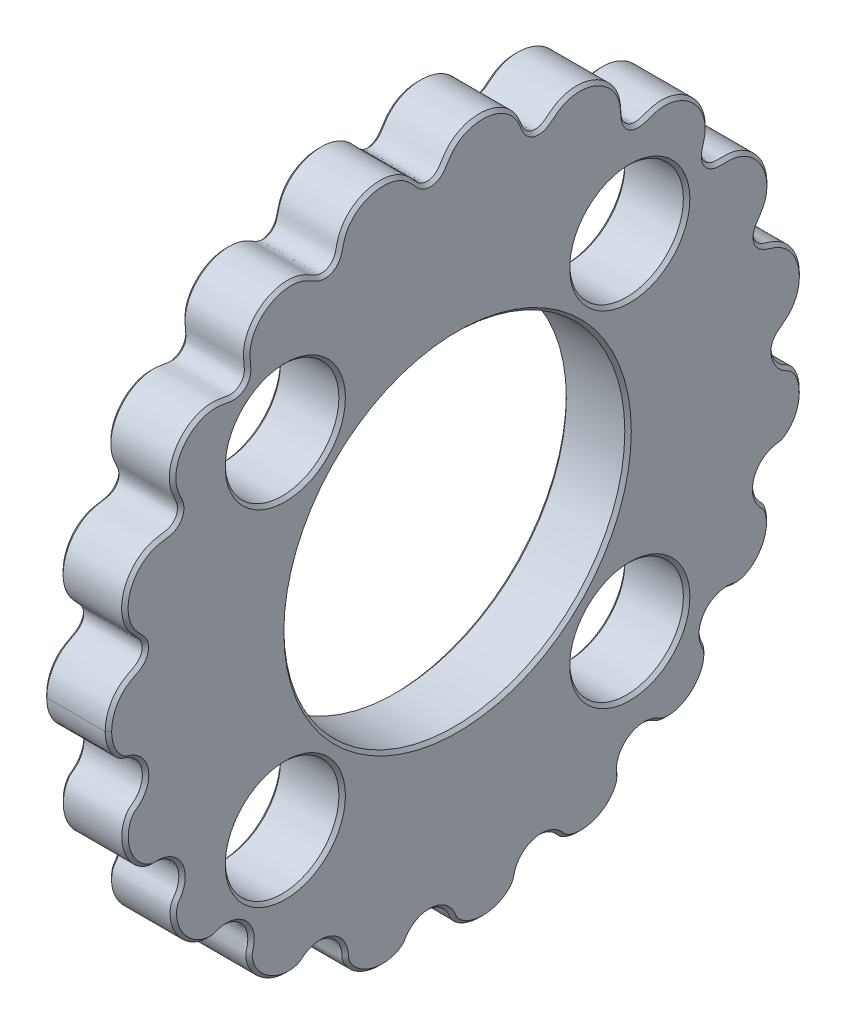
SolidWorks part; units mm, degrees
ref_plane "Ebene vorne" through (0, 0, 0) normal (0, 0, 1) x (1, 0, 0)
ref_plane "Ebene oben" through (0, 0, 0) normal (0, 1, 0) x (1, 0, 0)
ref_plane "Ebene rechts" through (0, 0, 0) normal (1, 0, 0) x (0, 0, -1)
sketch "Sketch3" plane through (0, 0, 0) normal (1, 0, 0) x (0, 0, -1)
  line L0 (-69.959, 0) -> (69.959, 0) construction
  line L1 (0, 0) -> (-10.6066, 10.6066) construction
  circle A0 centre (0, 0) radius 15
  circle A1 centre (-10.6066, 10.6066) radius 3.5
  circle A2 centre (10.6066, 10.6066) radius 3.5
  circle A3 centre (10.6066, -10.6066) radius 3.5
  circle A4 centre (-10.6066, -10.6066) radius 3.5
  circle A5 centre (0, 0) radius 10.5
  spline S0 degree 4 poles (20.1598, 5.1766) (20.2489, 5.1264) (20.4175, 5.0093) (20.6743, 4.7658) (20.9574, 4.3512) (21.1652, 3.8448) (21.2528, 3.3342) (21.2472, 2.8914) (21.1835, 2.5096) (21.0997, 2.2356) (20.9932, 1.9994) (20.8724, 1.8019) (20.7735, 1.6733) (20.6777, 1.5726) (20.5896, 1.4977) (20.5132, 1.4449) (20.4297, 1.4047) (20.3465, 1.3647) (20.2541, 1.3135) (20.1541, 1.2498) (20.0201, 1.1487) (19.8899, 1.0222) (19.7767, 0.8808) (19.6825, 0.7257) (19.6193, 0.5964) (19.5727, 0.4698) (19.5402, 0.3554) (19.5187, 0.2421) (19.5059, 0.1552) (19.4993, 0.0318) (19.4995, -0.0375) (19.5068, -0.1675) (19.5215, -0.258) (19.5435, -0.3688) (19.5726, -0.4665) (19.6088, -0.5678) (19.6518, -0.6633) (19.7141, -0.7811) (19.8021, -0.9144) (19.9055, -1.0376) (20.0225, -1.1477) (20.1279, -1.2303) (20.2164, -1.2904) (20.3096, -1.3452) (20.4065, -1.3948) (20.5072, -1.4399) (20.5986, -1.5037) (20.7026, -1.5958) (20.8136, -1.7205) (20.9519, -1.9189) (21.0919, -2.2037) (21.1991, -2.5525) (21.253, -2.9608) (21.242, -3.3883) (21.1596, -3.8246) (20.9993, -4.2562) (20.7847, -4.6139) (20.5518, -4.8847) (20.3196, -5.082) (20.148, -5.1902) (20.0018, -5.2562) (19.889, -5.2886) (19.823, -5.3) (19.7398, -5.3091) (19.6403, -5.323) (19.4926, -5.3532) (19.2396, -5.4344) (18.9193, -5.6134) (18.6087, -5.9329) (18.3998, -6.371) (18.3434, -6.7729) (18.3754, -7.0976) (18.4524, -7.3578) (18.5433, -7.556) (18.6476, -7.7183) (18.7538, -7.8482) (18.8534, -7.9501) (18.9388, -8.0314) (19.0057, -8.129) (19.0617, -8.2323) (19.1194, -8.3679) (19.1853, -8.5813) (19.2316, -8.8783) (19.2272, -9.2552) (19.1492, -9.6716) (19.0013, -10.0803) (18.7836, -10.4696) (18.4965, -10.8258) (18.141, -11.132) (17.8062, -11.3203) (17.5245, -11.4181) (17.3161, -11.4556) (17.1899, -11.4659) (17.0628, -11.4599) (16.9399, -11.4279) (16.784, -11.4013) (16.5943, -11.3863) (16.3722, -11.3993) (16.062, -11.4694) (15.7287, -11.6282) (15.4102, -11.9026) (15.166, -12.3004) (15.0661, -12.6812) (15.0617, -13.0152) (15.1059, -13.2618) (15.1556, -13.4248) (15.2052, -13.5453) (15.2437, -13.6271) (15.2853, -13.7075) (15.3299, -13.8198) (15.3611, -13.9838) (15.3718, -14.2441) (15.3234, -14.5815) (15.2018, -14.9515) (14.9918, -15.3365) (14.7188, -15.6829) (14.3906, -15.9822) (14.0151, -16.2248) (13.6521, -16.3784) (13.3247, -16.4596) (13.0704, -16.4859) (12.896, -16.486) (12.747, -16.4725) (12.6248, -16.4497) (12.5044, -16.4166) (12.3914, -16.3634) (12.2876, -16.2945) (12.1769, -16.2375) (12.0639, -16.1864) (11.9469, -16.1455) (11.798, -16.1056) (11.6151, -16.0774) (11.3989, -16.0731) (11.1004, -16.1161) (10.7645, -16.2398) (10.4271, -16.4766) (10.1791, -16.7994) (10.0441, -17.1159) (9.9845, -17.3978) (9.9735, -17.6032) (9.9836, -17.7825) (10.0093, -17.9343) (10.0096, -18.0577) (9.9909, -18.1796) (9.962, -18.2991) (9.9142, -18.4395) (9.8438, -18.5981) (9.7171, -18.8194) (9.5108, -19.0856) (9.2242, -19.3554) (8.8509, -19.6009) (8.4446, -19.7806) (8.0172, -19.8906) (7.5794, -19.9274) (7.192, -19.8889) (6.8645, -19.7971) (6.6325, -19.6823) (6.4834, -19.5805) (6.3828, -19.4695) (6.3085, -19.3763) (6.2049, -19.2713) (6.0725, -19.1566) (5.9023, -19.0444) (5.6924, -18.9467) (5.4174, -18.8669) (5.0761, -18.8384) (4.6713, -18.9063) (4.3021, -19.0948) (4.0341, -19.3363) (3.853, -19.5884) (3.7553, -19.7851) (3.6942, -19.965) (3.6579, -20.1211) (3.6359, -20.2479) (3.5855, -20.3669) (3.5231, -20.4788) (3.4349, -20.6053) (3.3176, -20.7414) (3.1252, -20.9211) (2.8393, -21.1182) (2.4722, -21.2912) (2.0318, -21.409) (1.5853, -21.4507) (1.1457, -21.4191) (0.7242, -21.3171) (0.3736, -21.162) (0.0963, -20.9776) (-0.0868, -20.8033) (-0.1954, -20.6677) (-0.2653, -20.5409) (-0.3023, -20.4313) (-0.3582, -20.3022) (-0.4357, -20.1551) (-0.5755, -19.9522) (-0.8096, -19.7201) (-1.1429, -19.5201) (-1.5298, -19.4209) (-1.8833, -19.4216) (-2.1824, -19.4863) (-2.4235, -19.5837) (-2.6177, -19.704) (-2.7683, -19.83) (-2.8819, -19.949) (-2.9651, -20.0526) (-3.0308, -20.1486) (-3.0815, -20.2343) (-3.1318, -20.3203) (-3.2149, -20.4245) (-3.3463, -20.5413) (-3.5281, -20.6607) (-3.8009, -20.7896) (-4.1396, -20.8903) (-4.5495, -20.9403) (-5.0055, -20.9124) (-5.4359, -20.8119) (-5.831, -20.6497) (-6.1835, -20.435) (-6.4602, -20.1949) (-6.6471, -19.9716) (-6.762, -19.789) (-6.8259, -19.6634) (-6.8684, -19.559) (-6.902, -19.4512) (-6.9203, -19.3396) (-6.9202, -19.2272) (-6.9287, -19.116) (-6.9432, -19.0058) (-6.9653, -18.8974) (-7.0023, -18.7642) (-7.0618, -18.609) (-7.176, -18.393) (-7.3782, -18.1405) (-7.6456, -17.9326) (-7.9665, -17.7915) (-8.2726, -17.7292) (-8.5479, -17.7238) (-8.7862, -17.7624) (-8.9831, -17.8259) (-9.1403, -17.8978) (-9.2605, -17.9671) (-9.3756, -18.0454) (-9.4814, -18.1347) (-9.5867, -18.2261) (-9.7115, -18.2894) (-9.8659, -18.3496) (-10.0545, -18.3955) (-10.2734, -18.4226) (-10.5217, -18.4222) (-10.8297, -18.3877) (-11.191, -18.2958) (-11.5863, -18.1244) (-11.9914, -17.8524) (-12.3379, -17.5156) (-12.5789, -17.1733) (-12.7328, -16.8493) (-12.8091, -16.5879) (-12.841, -16.4031) (-12.8477, -16.2421) (-12.8408, -16.1054) (-12.8012, -15.975) (-12.762, -15.8451) (-12.7361, -15.7115) (-12.72, -15.5767) (-12.7133, -15.3409) (-12.762, -15.0062) (-12.9287, -14.6233) (-13.2603, -14.2612) (-13.6131, -14.0585) (-13.9228, -13.9677) (-14.1874, -13.9415) (-14.3979, -13.9495) (-14.5819, -13.9821) (-14.7389, -14.0276) (-14.8688, -14.0787) (-14.9772, -14.1217) (-15.0926, -14.141) (-15.2084, -14.1497) (-15.354, -14.1467) (-15.5742, -14.1203) (-15.8631, -14.0426) (-16.2049, -13.8866) (-16.5536, -13.6476) (-16.8676, -13.3477) (-17.1359, -12.9915) (-17.3463, -12.5846) (-17.4827, -12.1351) (-17.5233, -11.7179) (-17.4872, -11.3856) (-17.4137, -11.1474) (-17.3356, -11.0026) (-17.2532, -10.9001) (-17.1662, -10.7612) (-17.0775, -10.5876) (-17.0048, -10.3733) (-16.953, -10.0569) (-16.9754, -9.6908) (-17.108, -9.2976) (-17.3815, -8.9223) (-17.6948, -8.6844) (-18.0059, -8.5517) (-18.2577, -8.4983) (-18.4304, -8.484) (-18.5768, -8.4833) (-18.6963, -8.4942) (-18.846, -8.4822) (-19.02, -8.4351) (-19.2565, -8.3348) (-19.5373, -8.1524) (-19.8177, -7.8936) (-20.0766, -7.552) (-20.2797, -7.1665) (-20.4201, -6.7458) (-20.4899, -6.3001) (-20.4812, -5.8985) (-20.4188, -5.5606) (-20.3355, -5.3148) (-20.2618, -5.1556) (-20.1868, -5.0267) (-20.1153, -4.9277) (-20.0353, -4.834) (-19.9381, -4.7591) (-19.8365, -4.6909) (-19.7422, -4.6127) (-19.6292, -4.5071) (-19.507, -4.3649) (-19.3869, -4.1805) (-19.286, -3.9488) (-19.2151, -3.6655) (-19.2002, -3.3332) (-19.2616, -3.0164) (-19.3873, -2.7331) (-19.5327, -2.5197) (-19.672, -2.3657) (-19.8304, -2.2321) (-19.9833, -2.1352) (-20.1221, -2.0671) (-20.2418, -2.0207) (-20.3392, -1.9882) (-20.4387, -1.9626) (-20.5341, -1.9237) (-20.6351, -1.8649) (-20.7411, -1.7884) (-20.8788, -1.6657) (-21.0357, -1.486) (-21.1893, -1.254) (-21.314, -0.9913) (-21.3989, -0.7437) (-21.4473, -0.5393) (-21.4733, -0.3884) (-21.4883, -0.2556) (-21.4963, -0.1623) (-21.5004, -0.0324) (-21.5003, 0.0419) (-21.4955, 0.1832) (-21.4855, 0.2823) (-21.4707, 0.4047) (-21.4508, 0.5144) (-21.4198, 0.657) (-21.3725, 0.8223) (-21.3028, 1.0125) (-21.2028, 1.2203) (-21.0822, 1.4173) (-20.9568, 1.5792) (-20.8332, 1.7075) (-20.7176, 1.8065) (-20.6146, 1.8778) (-20.5048, 1.9405) (-20.3843, 1.9771) (-20.2637, 2.0114) (-20.1466, 2.0573) (-20.0068, 2.1227) (-19.8498, 2.2182) (-19.6838, 2.3514) (-19.5215, 2.5308) (-19.363, 2.7742) (-19.2381, 3.0912) (-19.1788, 3.5444) (-19.2823, 4.0223) (-19.4989, 4.3828) (-19.7335, 4.6102) (-19.8718, 4.7151) (-19.943, 4.7645) (-19.9775, 4.7908) (-19.9945, 4.8043) knots 0 0 0 0 0 0.00445 0.008901 0.015291 0.021681 0.028072 0.031267 0.034462 0.038485 0.040497 0.042509 0.04452 0.045526 0.046532 0.047538 0.048544 0.049549 0.050555 0.052128 0.053701 0.056847 0.058419 0.059992 0.061565 0.063138 0.06421 0.065282 0.066355 0.067427 0.068575 0.069724 0.070872 0.072021 0.073169 0.074318 0.075467 0.076615 0.078942 0.08127 0.082433 0.083597 0.08476 0.085924 0.087131 0.088338 0.089545 0.090753 0.093167 0.095581 0.100042 0.104502 0.108963 0.113423 0.118578 0.123733 0.128888 0.131466 0.134043 0.136956 0.137684 0.138412 0.13914 0.139868 0.141325 0.142781 0.145694 0.1514 0.157107 0.161784 0.166461 0.168825 0.171189 0.173553 0.175916 0.177195 0.178475 0.179754 0.181033 0.182312 0.183591 0.186149 0.190735 0.195322 0.199908 0.204495 0.209568 0.214641 0.219714 0.224787 0.226163 0.227539 0.228915 0.230291 0.231667 0.233043 0.235794 0.23855 0.241306 0.246818 0.251681 0.256544 0.26132 0.263709 0.266097 0.267408 0.26872 0.269375 0.270031 0.271342 0.273965 0.276587 0.281332 0.286077 0.290822 0.295567 0.30044 0.305313 0.310187 0.312623 0.31506 0.316413 0.317766 0.319118 0.320471 0.321824 0.323176 0.324529 0.325882 0.32722 0.328558 0.331235 0.333911 0.336587 0.341625 0.346663 0.35157 0.354024 0.356477 0.359151 0.360488 0.361825 0.363162 0.364499 0.365835 0.367172 0.369606 0.372039 0.376905 0.381772 0.386639 0.391391 0.396144 0.400896 0.405649 0.408244 0.41084 0.412138 0.413436 0.414733 0.416031 0.418542 0.421052 0.423562 0.426073 0.430951 0.435829 0.441158 0.443823 0.446488 0.449278 0.450673 0.452068 0.453463 0.454858 0.456253 0.457648 0.460155 0.462663 0.467679 0.472695 0.47771 0.482404 0.487098 0.491792 0.496485 0.498994 0.501503 0.502758 0.504012 0.505266 0.506521 0.508878 0.511236 0.51595 0.520754 0.525557 0.528373 0.531188 0.534004 0.53682 0.538264 0.539709 0.541153 0.542597 0.543319 0.544041 0.545485 0.548374 0.550925 0.553476 0.558578 0.56368 0.568782 0.573252 0.577722 0.582192 0.586662 0.589112 0.590337 0.591563 0.592788 0.594013 0.595238 0.596463 0.597665 0.598868 0.60007 0.601273 0.603677 0.606082 0.610663 0.615244 0.618223 0.621202 0.624181 0.62716 0.628669 0.630178 0.631688 0.633197 0.634706 0.636215 0.637725 0.639234 0.641927 0.644619 0.647312 0.650005 0.65539 0.660775 0.665949 0.671124 0.676298 0.678885 0.681473 0.682949 0.684426 0.685902 0.687379 0.688856 0.690332 0.691809 0.693286 0.699103 0.704921 0.709604 0.714288 0.716571 0.718854 0.721138 0.723421 0.724685 0.72595 0.727214 0.728479 0.729743 0.731008 0.733537 0.738115 0.742692 0.74727 0.751847 0.756929 0.762011 0.767092 0.772174 0.775025 0.77645 0.777875 0.7793 0.780725 0.783576 0.786336 0.789097 0.794618 0.799358 0.804098 0.809026 0.81149 0.813954 0.815255 0.816556 0.817857 0.819158 0.82176 0.824362 0.829001 0.83364 0.83828 0.842919 0.847883 0.852848 0.857813 0.860295 0.862778 0.864108 0.865439 0.86677 0.868101 0.869431 0.870762 0.872093 0.873423 0.876159 0.878894 0.88163 0.884365 0.888808 0.893251 0.895503 0.897755 0.900008 0.90226 0.904493 0.905609 0.906725 0.907841 0.908958 0.910074 0.91119 0.912915 0.914639 0.918087 0.921535 0.924984 0.927236 0.929487 0.930613 0.931739 0.932865 0.933991 0.935244 0.936498 0.937752 0.939005 0.940259 0.941513 0.94402 0.946528 0.949035 0.951542 0.95405 0.955415 0.95678 0.958145 0.95951 0.960875 0.96224 0.963605 0.96497 0.96759 0.97021 0.97283 0.975451 0.980179 0.984906 0.992453 0.996227 0.998113 0.999057 1 1 1 1 1 construction
  spline S1 degree 4 poles (19.5, 0) (19.5, -0.0229) (19.5012, -0.0684) (19.5068, -0.1675) (19.5215, -0.258) (19.5435, -0.3688) (19.5726, -0.4665) (19.6088, -0.5678) (19.6518, -0.6633) (19.7141, -0.7811) (19.8021, -0.9144) (19.9055, -1.0376) (20.0225, -1.1477) (20.1279, -1.2303) (20.2164, -1.2904) (20.3096, -1.3452) (20.4065, -1.3948) (20.5072, -1.4399) (20.5986, -1.5037) (20.7026, -1.5958) (20.8136, -1.7205) (20.9519, -1.9189) (21.0919, -2.2037) (21.1991, -2.5525) (21.253, -2.9608) (21.242, -3.3883) (21.1596, -3.8246) (20.9993, -4.2562) (20.7847, -4.6139) (20.5518, -4.8847) (20.3196, -5.082) (20.148, -5.1902) (20.0018, -5.2562) (19.889, -5.2886) (19.823, -5.3) (19.7398, -5.3091) (19.6403, -5.323) (19.4926, -5.3532) (19.2396, -5.4344) (18.9193, -5.6134) (18.6087, -5.9329) (18.3998, -6.371) (18.3434, -6.7729) (18.3754, -7.0976) (18.4524, -7.3578) (18.5433, -7.556) (18.6476, -7.7183) (18.7538, -7.8482) (18.8534, -7.9501) (18.9388, -8.0314) (19.0057, -8.129) (19.0617, -8.2323) (19.1194, -8.3679) (19.1853, -8.5813) (19.2316, -8.8783) (19.2272, -9.2552) (19.1492, -9.6716) (19.0013, -10.0803) (18.7836, -10.4696) (18.4965, -10.8258) (18.141, -11.132) (17.8062, -11.3203) (17.5245, -11.4181) (17.3161, -11.4556) (17.1899, -11.4659) (17.0628, -11.4599) (16.9399, -11.4279) (16.784, -11.4013) (16.5943, -11.3863) (16.3722, -11.3993) (16.062, -11.4694) (15.7287, -11.6282) (15.4102, -11.9026) (15.166, -12.3004) (15.0661, -12.6812) (15.0617, -13.0152) (15.1059, -13.2618) (15.1556, -13.4248) (15.2052, -13.5453) (15.2437, -13.6271) (15.2853, -13.7075) (15.3299, -13.8198) (15.3611, -13.9838) (15.3718, -14.2441) (15.3234, -14.5815) (15.2018, -14.9515) (14.9918, -15.3365) (14.7188, -15.6829) (14.3906, -15.9822) (14.0151, -16.2248) (13.6521, -16.3784) (13.3247, -16.4596) (13.0704, -16.4859) (12.896, -16.486) (12.747, -16.4725) (12.6248, -16.4497) (12.5044, -16.4166) (12.3914, -16.3634) (12.2876, -16.2945) (12.1769, -16.2375) (12.0639, -16.1864) (11.9469, -16.1455) (11.798, -16.1056) (11.6151, -16.0774) (11.3989, -16.0731) (11.1004, -16.1161) (10.7645, -16.2398) (10.4271, -16.4766) (10.1791, -16.7994) (10.0441, -17.1159) (9.9845, -17.3978) (9.9735, -17.6032) (9.9836, -17.7825) (10.0093, -17.9343) (10.0096, -18.0577) (9.9909, -18.1796) (9.962, -18.2991) (9.9142, -18.4395) (9.8438, -18.5981) (9.7171, -18.8194) (9.5108, -19.0856) (9.2242, -19.3554) (8.8509, -19.6009) (8.4446, -19.7806) (8.0172, -19.8906) (7.5794, -19.9274) (7.192, -19.8889) (6.8645, -19.7971) (6.6325, -19.6823) (6.4834, -19.5805) (6.3828, -19.4695) (6.3085, -19.3763) (6.2049, -19.2713) (6.0725, -19.1566) (5.9023, -19.0444) (5.6924, -18.9467) (5.4174, -18.8669) (5.0761, -18.8384) (4.6713, -18.9063) (4.3021, -19.0948) (4.0341, -19.3363) (3.853, -19.5884) (3.7553, -19.7851) (3.6942, -19.965) (3.6579, -20.1211) (3.6359, -20.2479) (3.5855, -20.3669) (3.5231, -20.4788) (3.4349, -20.6053) (3.3176, -20.7414) (3.1252, -20.9211) (2.8393, -21.1182) (2.4722, -21.2912) (2.0318, -21.409) (1.5853, -21.4507) (1.1457, -21.4191) (0.7242, -21.3171) (0.3736, -21.162) (0.0963, -20.9776) (-0.0868, -20.8033) (-0.1954, -20.6677) (-0.2653, -20.5409) (-0.3023, -20.4313) (-0.3582, -20.3022) (-0.4357, -20.1551) (-0.5755, -19.9522) (-0.8096, -19.7201) (-1.1429, -19.5201) (-1.5298, -19.4209) (-1.8833, -19.4216) (-2.1824, -19.4863) (-2.4235, -19.5837) (-2.6177, -19.704) (-2.7683, -19.83) (-2.8819, -19.949) (-2.9651, -20.0526) (-3.0308, -20.1486) (-3.0815, -20.2343) (-3.1318, -20.3203) (-3.2149, -20.4245) (-3.3463, -20.5413) (-3.5281, -20.6607) (-3.8009, -20.7896) (-4.1396, -20.8903) (-4.5495, -20.9403) (-5.0055, -20.9124) (-5.4359, -20.8119) (-5.831, -20.6497) (-6.1835, -20.435) (-6.4602, -20.1949) (-6.6471, -19.9716) (-6.762, -19.789) (-6.8259, -19.6634) (-6.8684, -19.559) (-6.902, -19.4512) (-6.9203, -19.3396) (-6.9202, -19.2272) (-6.9287, -19.116) (-6.9432, -19.0058) (-6.9653, -18.8974) (-7.0023, -18.7642) (-7.0618, -18.609) (-7.176, -18.393) (-7.3782, -18.1405) (-7.6456, -17.9326) (-7.9665, -17.7915) (-8.2726, -17.7292) (-8.5479, -17.7238) (-8.7862, -17.7624) (-8.9831, -17.8259) (-9.1403, -17.8978) (-9.2605, -17.9671) (-9.3756, -18.0454) (-9.4814, -18.1347) (-9.5867, -18.2261) (-9.7115, -18.2894) (-9.8659, -18.3496) (-10.0545, -18.3955) (-10.2734, -18.4226) (-10.5217, -18.4222) (-10.8297, -18.3877) (-11.191, -18.2958) (-11.5863, -18.1244) (-11.9914, -17.8524) (-12.3379, -17.5156) (-12.5789, -17.1733) (-12.7328, -16.8493) (-12.8091, -16.5879) (-12.841, -16.4031) (-12.8477, -16.2421) (-12.8408, -16.1054) (-12.8012, -15.975) (-12.762, -15.8451) (-12.7361, -15.7115) (-12.72, -15.5767) (-12.7133, -15.3409) (-12.762, -15.0062) (-12.9287, -14.6233) (-13.2603, -14.2612) (-13.6131, -14.0585) (-13.9228, -13.9677) (-14.1874, -13.9415) (-14.3979, -13.9495) (-14.5819, -13.9821) (-14.7389, -14.0276) (-14.8688, -14.0787) (-14.9772, -14.1217) (-15.0926, -14.141) (-15.2084, -14.1497) (-15.354, -14.1467) (-15.5742, -14.1203) (-15.8631, -14.0426) (-16.2049, -13.8866) (-16.5536, -13.6476) (-16.8676, -13.3477) (-17.1359, -12.9915) (-17.3463, -12.5846) (-17.4827, -12.1351) (-17.5233, -11.7179) (-17.4872, -11.3856) (-17.4137, -11.1474) (-17.3356, -11.0026) (-17.2532, -10.9001) (-17.1662, -10.7612) (-17.0775, -10.5876) (-17.0048, -10.3733) (-16.953, -10.0569) (-16.9754, -9.6908) (-17.108, -9.2976) (-17.3815, -8.9223) (-17.6948, -8.6844) (-18.0059, -8.5517) (-18.2577, -8.4983) (-18.4304, -8.484) (-18.5768, -8.4833) (-18.6963, -8.4942) (-18.846, -8.4822) (-19.02, -8.4351) (-19.2565, -8.3348) (-19.5373, -8.1524) (-19.8177, -7.8936) (-20.0766, -7.552) (-20.2797, -7.1665) (-20.4201, -6.7458) (-20.4899, -6.3001) (-20.4812, -5.8985) (-20.4188, -5.5606) (-20.3355, -5.3148) (-20.2618, -5.1556) (-20.1868, -5.0267) (-20.1153, -4.9277) (-20.0353, -4.834) (-19.9381, -4.7591) (-19.8365, -4.6909) (-19.7422, -4.6127) (-19.6292, -4.5071) (-19.507, -4.3649) (-19.3869, -4.1805) (-19.286, -3.9488) (-19.2151, -3.6655) (-19.2002, -3.3332) (-19.2616, -3.0164) (-19.3873, -2.7331) (-19.5327, -2.5197) (-19.672, -2.3657) (-19.8304, -2.2321) (-19.9833, -2.1352) (-20.1221, -2.0671) (-20.2418, -2.0207) (-20.3392, -1.9882) (-20.4387, -1.9626) (-20.5341, -1.9237) (-20.6351, -1.8649) (-20.7411, -1.7884) (-20.8788, -1.6657) (-21.0357, -1.486) (-21.1893, -1.254) (-21.314, -0.9913) (-21.3989, -0.7437) (-21.4473, -0.5393) (-21.4733, -0.3884) (-21.4883, -0.2556) (-21.4963, -0.1623) (-21.4993, -0.0676) (-21.5, -0.0224) (-21.5, 0) knots 0.067427 0.067427 0.067427 0.067427 0.067427 0.068575 0.069724 0.070872 0.072021 0.073169 0.074318 0.075467 0.076615 0.078942 0.08127 0.082433 0.083597 0.08476 0.085924 0.087131 0.088338 0.089545 0.090753 0.093167 0.095581 0.100042 0.104502 0.108963 0.113423 0.118578 0.123733 0.128888 0.131466 0.134043 0.136956 0.137684 0.138412 0.13914 0.139868 0.141325 0.142781 0.145694 0.1514 0.157107 0.161784 0.166461 0.168825 0.171189 0.173553 0.175916 0.177195 0.178475 0.179754 0.181033 0.182312 0.183591 0.186149 0.190735 0.195322 0.199908 0.204495 0.209568 0.214641 0.219714 0.224787 0.226163 0.227539 0.228915 0.230291 0.231667 0.233043 0.235794 0.23855 0.241306 0.246818 0.251681 0.256544 0.26132 0.263709 0.266097 0.267408 0.26872 0.269375 0.270031 0.271342 0.273965 0.276587 0.281332 0.286077 0.290822 0.295567 0.30044 0.305313 0.310187 0.312623 0.31506 0.316413 0.317766 0.319118 0.320471 0.321824 0.323176 0.324529 0.325882 0.32722 0.328558 0.331235 0.333911 0.336587 0.341625 0.346663 0.35157 0.354024 0.356477 0.359151 0.360488 0.361825 0.363162 0.364499 0.365835 0.367172 0.369606 0.372039 0.376905 0.381772 0.386639 0.391391 0.396144 0.400896 0.405649 0.408244 0.41084 0.412138 0.413436 0.414733 0.416031 0.418542 0.421052 0.423562 0.426073 0.430951 0.435829 0.441158 0.443823 0.446488 0.449278 0.450673 0.452068 0.453463 0.454858 0.456253 0.457648 0.460155 0.462663 0.467679 0.472695 0.47771 0.482404 0.487098 0.491792 0.496485 0.498994 0.501503 0.502758 0.504012 0.505266 0.506521 0.508878 0.511236 0.51595 0.520754 0.525557 0.528373 0.531188 0.534004 0.53682 0.538264 0.539709 0.541153 0.542597 0.543319 0.544041 0.545485 0.548374 0.550925 0.553476 0.558578 0.56368 0.568782 0.573252 0.577722 0.582192 0.586662 0.589112 0.590337 0.591563 0.592788 0.594013 0.595238 0.596463 0.597665 0.598868 0.60007 0.601273 0.603677 0.606082 0.610663 0.615244 0.618223 0.621202 0.624181 0.62716 0.628669 0.630178 0.631688 0.633197 0.634706 0.636215 0.637725 0.639234 0.641927 0.644619 0.647312 0.650005 0.65539 0.660775 0.665949 0.671124 0.676298 0.678885 0.681473 0.682949 0.684426 0.685902 0.687379 0.688856 0.690332 0.691809 0.693286 0.699103 0.704921 0.709604 0.714288 0.716571 0.718854 0.721138 0.723421 0.724685 0.72595 0.727214 0.728479 0.729743 0.731008 0.733537 0.738115 0.742692 0.74727 0.751847 0.756929 0.762011 0.767092 0.772174 0.775025 0.77645 0.777875 0.7793 0.780725 0.783576 0.786336 0.789097 0.794618 0.799358 0.804098 0.809026 0.81149 0.813954 0.815255 0.816556 0.817857 0.819158 0.82176 0.824362 0.829001 0.83364 0.83828 0.842919 0.847883 0.852848 0.857813 0.860295 0.862778 0.864108 0.865439 0.86677 0.868101 0.869431 0.870762 0.872093 0.873423 0.876159 0.878894 0.88163 0.884365 0.888808 0.893251 0.895503 0.897755 0.900008 0.90226 0.904493 0.905609 0.906725 0.907841 0.908958 0.910074 0.91119 0.912915 0.914639 0.918087 0.921535 0.924984 0.927236 0.929487 0.930613 0.931739 0.932865 0.933991 0.933991 0.933991 0.933991 0.933991
  spline S2 degree 4 poles (19.5, 0) (19.5, 0.0069) (19.5002, 0.0208) (19.5012, 0.0454) (19.5038, 0.0811) (19.5087, 0.124) (19.5171, 0.1718) (19.5307, 0.2276) (19.5512, 0.2905) (19.583, 0.3664) (19.6326, 0.4578) (19.7063, 0.5592) (19.8083, 0.6647) (19.9241, 0.7621) (20.0449, 0.853) (20.1666, 0.9428) (20.3162, 1.0583) (20.5051, 1.2222) (20.7167, 1.4512) (20.9249, 1.761) (21.0904, 2.1211) (21.1996, 2.5033) (21.2522, 2.8985) (21.2472, 3.3989) (21.1487, 3.893) (20.9599, 4.3605) (20.6852, 4.7806) (20.4169, 5.0797) (20.1203, 5.3177) (19.81, 5.4965) (19.4976, 5.6209) (19.1986, 5.7133) (18.8465, 5.8278) (18.4993, 6.0927) (18.3446, 6.5197) (18.4364, 6.9401) (18.6307, 7.244) (18.8047, 7.4895) (18.976, 7.7672) (19.1182, 8.0861) (19.243, 8.5414) (19.2743, 9.1407) (19.1367, 9.8327) (18.7665, 10.5509) (18.2793, 11.0675) (17.768, 11.3934) (17.3164, 11.5591) (16.9649, 11.6294) (16.629, 11.6472) (16.3158, 11.6383) (15.9458, 11.6301) (15.5294, 11.7614) (15.2394, 12.1109) (15.1831, 12.5374) (15.2653, 12.8886) (15.3505, 13.1768) (15.4236, 13.4945) (15.4566, 13.8417) (15.4296, 14.3126) (15.2679, 14.8903) (14.9164, 15.502) (14.3357, 16.0641) (13.7085, 16.3979) (13.1194, 16.5434) (12.6383, 16.5561) (12.2825, 16.5104) (11.9584, 16.4197) (11.6644, 16.3102) (11.3179, 16.1806) (10.8791, 16.1627) (10.4882, 16.3953) (10.2937, 16.7757) (10.2543, 17.1287) (10.2416, 17.4182) (10.2116, 17.7365) (10.1361, 18.0752) (9.9627, 18.5192) (9.6202, 19.0276) (9.0785, 19.5057) (8.422, 19.8117) (7.812, 19.9332) (7.296, 19.9312) (6.8884, 19.8651) (6.5215, 19.7399) (6.2019, 19.5712) (5.9299, 19.3743) (5.6936, 19.1763) (5.4006, 18.9483) (4.9835, 18.8183) (4.5485, 18.9392) (4.2622, 19.252) (4.1214, 19.5708) (4.0147, 19.8392) (3.8811, 20.1246) (3.699, 20.4113) (3.3965, 20.7605) (2.9201, 21.1183) (2.2691, 21.3905) (1.4617, 21.4836) (0.7524, 21.363) (0.1911, 21.1134) (-0.2019, 20.8228) (-0.4582, 20.5621) (-0.6614, 20.2833) (-0.8287, 20.008) (-1.0321, 19.6874) (-1.3848, 19.4207) (-1.8362, 19.3885) (-2.2098, 19.5846) (-2.4483, 19.8387) (-2.6358, 20.0579) (-2.8537, 20.2852) (-3.1174, 20.4985) (-3.5152, 20.7327) (-4.0807, 20.9196) (-4.7846, 20.9694) (-5.5795, 20.7993) (-6.2133, 20.4578) (-6.6657, 20.0416) (-6.9453, 19.6406) (-7.1052, 19.3114) (-7.2083, 18.9821) (-7.2781, 18.6671) (-7.3641, 18.2975) (-7.6052, 17.9271) (-8.019, 17.744) (-8.4369, 17.8017) (-8.7462, 17.9622) (-8.9943, 18.1087) (-9.2733, 18.254) (-9.591, 18.3719) (-10.0423, 18.4667) (-10.6376, 18.4633) (-11.3205, 18.2854) (-12.0194, 17.8699) (-12.5109, 17.3433) (-12.8066, 16.804) (-12.9436, 16.3343) (-12.99, 15.9711) (-12.9822, 15.6259) (-12.9467, 15.3049) (-12.9059, 14.9277) (-13.0077, 14.4951) (-13.3415, 14.1788) (-13.7656, 14.0958) (-14.122, 14.1526) (-14.4168, 14.2131) (-14.7401, 14.258) (-15.0894, 14.2594) (-15.5565, 14.1899) (-16.1175, 13.9767) (-16.6953, 13.5718) (-17.2031, 12.9434) (-17.4794, 12.2894) (-17.5714, 11.6902) (-17.5408, 11.2103) (-17.4634, 10.8604) (-17.3442, 10.5458) (-17.2101, 10.2628) (-17.0546, 9.9269) (-17.0098, 9.4925) (-17.2153, 9.0876) (-17.5844, 8.8666) (-17.9393, 8.8018) (-18.2375, 8.7639) (-18.5579, 8.7027) (-18.889, 8.5928) (-19.3091, 8.378) (-19.7725, 7.997) (-20.1905, 7.4286) (-20.4706, 6.6706) (-20.5233, 5.9622) (-20.4187, 5.3646) (-20.2365, 4.9193) (-20.0509, 4.6123) (-19.8377, 4.3523) (-19.6185, 4.1273) (-19.3622, 3.8616) (-19.2006, 3.5295) (-19.2104, 3.1696) (-19.3552, 2.8636) (-19.5458, 2.6644) (-19.7809, 2.5221) (-20.0305, 2.3996) (-20.3004, 2.2535) (-20.5769, 2.061) (-20.8429, 1.8092) (-21.082, 1.4946) (-21.2518, 1.1797) (-21.3554, 0.9099) (-21.4152, 0.6968) (-21.448, 0.548) (-21.4689, 0.4258) (-21.4827, 0.3231) (-21.4913, 0.2246) (-21.4972, 0.1475) (-21.4993, 0.0644) (-21.5, 0.0258) (-21.5, 0) knots 0.079192 0.079192 0.079192 0.079192 0.079192 0.079543 0.079894 0.080246 0.080597 0.0813 0.082002 0.082705 0.083407 0.084813 0.086426 0.088039 0.089653 0.091266 0.09288 0.094493 0.09772 0.101931 0.106143 0.110354 0.114565 0.118835 0.123104 0.131643 0.135913 0.140182 0.144452 0.148721 0.152068 0.155415 0.158762 0.162108 0.167807 0.173423 0.176647 0.17987 0.183094 0.186318 0.190525 0.194732 0.203147 0.211691 0.220236 0.22878 0.233052 0.237325 0.240674 0.244023 0.247372 0.250721 0.256422 0.262033 0.265254 0.268475 0.271695 0.274916 0.279119 0.283323 0.291729 0.300279 0.308829 0.317378 0.321653 0.325928 0.329279 0.33263 0.335982 0.339333 0.345038 0.350755 0.353861 0.356967 0.360073 0.363179 0.367462 0.371745 0.380312 0.389087 0.397862 0.40225 0.406637 0.411025 0.415413 0.418713 0.422012 0.425312 0.428612 0.434467 0.439986 0.443078 0.44617 0.449263 0.452355 0.45649 0.460625 0.468894 0.477549 0.486204 0.49486 0.499187 0.503515 0.506963 0.510411 0.513859 0.517307 0.523082 0.528596 0.531685 0.534775 0.537864 0.540954 0.545084 0.549215 0.557477 0.566137 0.574798 0.583458 0.587788 0.592119 0.595569 0.599019 0.602469 0.605919 0.611698 0.617206 0.620293 0.623379 0.626466 0.629552 0.633679 0.637806 0.64606 0.654725 0.663391 0.672057 0.67639 0.680722 0.684175 0.687627 0.691079 0.694531 0.700313 0.705931 0.709155 0.71238 0.715605 0.71883 0.723038 0.727247 0.735664 0.744207 0.752749 0.761292 0.765563 0.769835 0.773183 0.776531 0.779879 0.783228 0.788928 0.794541 0.797763 0.800984 0.804206 0.807428 0.811632 0.815837 0.824246 0.832794 0.841342 0.84989 0.854164 0.858438 0.861789 0.865139 0.868489 0.87184 0.877544 0.880347 0.88315 0.886115 0.889081 0.892047 0.895013 0.899212 0.903411 0.90761 0.91181 0.914422 0.915728 0.917034 0.91834 0.919646 0.920299 0.920952 0.922258 0.922258 0.922258 0.922258 0.922258
  point P8 (0, 0)
  point P22 (0, 0)
  dimension "D1" = 30
  dimension "D2" = 7
  dimension "D4" = 21
  dimension "D5" = 45
  dimension "D3" = 4
extrude "Boss-Extrude1" add sketch "Sketch3" along normal blind 4 contours S1 S2 A4 A0 A1 A2 A3 | A4 A0 A3 A2 A1 A5
chamfer "Chamfer1" distance 0.2 angle 45 14 edges at (0, 0, -10.5) (4, 0, -10.5) (4, -10.6066, -14.1066) (0, -10.6066, -14.1066) (0, -10.6066, 7.1066) (0, 10.6066, -14.1066) (4, 10.6066, 7.1066) (0, 10.6066, 7.1066) (4, -10.6066, 7.1066) (4, 10.6066, -14.1066)
equation "\"R\"= 30mm"
equation "\"E\"= 1mm"
equation "\"Rr\"= 3 / 2mm"
equation "\"N\"= 20"
